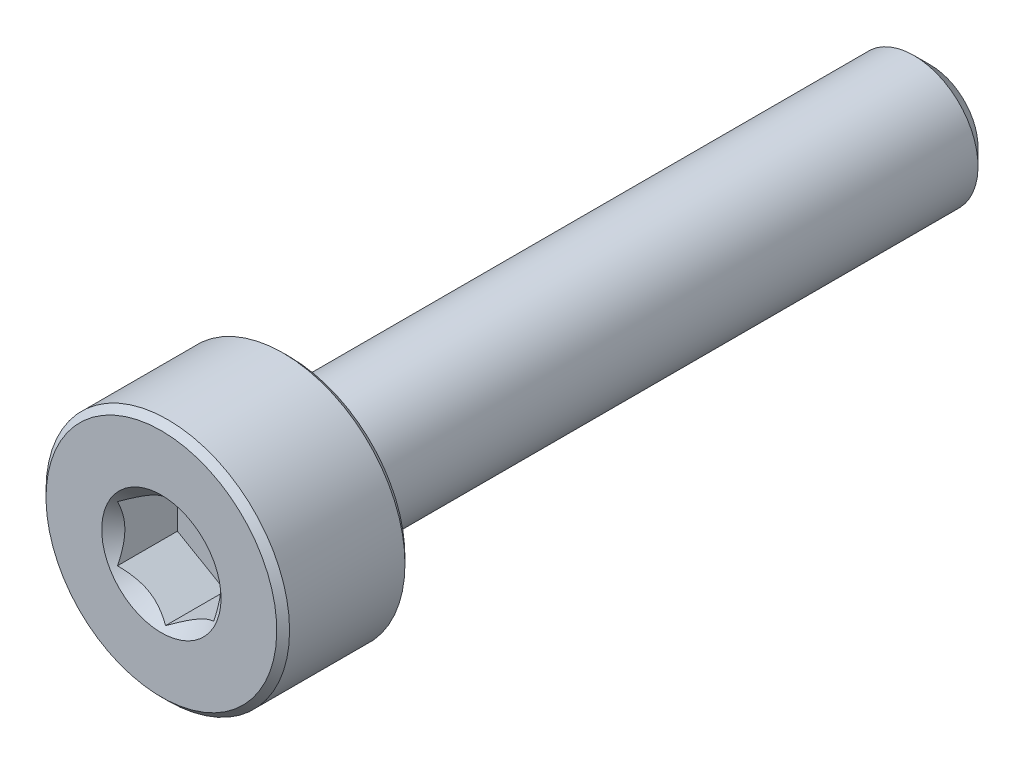
SolidWorks part; units mm, degrees
material "Alloy Steel (SS)"
ref_plane "Front Plane" through (0, 0, 0) normal (0, 0, 1) x (1, 0, 0)
ref_plane "Top Plane" through (0, 0, 0) normal (0, 1, 0) x (1, 0, 0)
ref_plane "Right Plane" through (0, 0, 0) normal (1, 0, 0) x (0, 0, -1)
sketch "Sketch1" plane through (0, 0, 0) normal (1, 0, 0) x (0, 0, -1)
  line L0 (-6, 0) -> (6, 0) construction
  line L1 (6, 0) -> (6, 0.7402) construction
  line L2 (6, 0.7402) -> (5.7402, 1) construction
  line L3 (5.7402, 1) -> (5.7, 1) construction
  line L4 (5.7, 1) -> (-4, 1) construction
  line L5 (-4, 1) -> (-4, 1.9) construction
  line L6 (-4, 1.9) -> (-6, 1.9) construction
  line L7 (-6, 1.9) -> (-6, 0) construction
  line L8 (6, 0.7402) -> (6, 1) construction
  line L9 (5.975, 1.0433) -> (6.175, 0.6969) construction
  line L10 (6.175, 0.6969) -> (6.375, 1.0433) construction
  line L11 (6.375, 1.0433) -> (5.975, 1.0433) construction
  line L12 (6.175, 1.0433) -> (6.175, 1) construction
  line L13 (6.175, 0.6969) -> (6.175, 0.7402) construction
  line L14 (6.15, 0.7402) -> (6.2, 0.7402) construction
  line L15 (6, 1) -> (6.35, 1) construction
  line L16 (5.9875, 1.0217) -> (6.3625, 1.0217) construction
  line L17 (6, 0) -> (6, -1) construction
  line L18 (-4.1, 1.9) -> (-4, 1.8) construction
  line L19 (-5.9, 1.9) -> (-6, 1.8) construction
  line L20 (-4, 1) -> (-4, 0) construction
  line L21 (-4, 0.5) -> (-0.6667, 0.5) construction
  line L22 (-0.6667, 0.5) -> (2.6667, 0.5) construction
  line L23 (2.6667, 0.5) -> (6, 0.5) construction
  line L24 (-0.6667, 0.5) -> (-0.6667, 1) construction
  line L25 (-0.6667, 1) -> (-0.6667, 1.9) construction
  line L26 (2.6667, 0.5) -> (2.6667, 1.9) construction
  point P0 (-6, 0.75)
  point P3 (5, 1)
  point P4 (0, 0)
  point P18 (2.6667, 1)
  point P22 (6.175, 0.7402)
  point P24 (5.7, 1)
  point P25 (6.175, 1)
  point P28 (6.175, 1.0217)
  point P29 (5, -1)
  point P30 (-0.6667, 1)
  point P31 (-5, 1.9)
  point P37 (-4.35, 1.9)
  point P38 (-5.85, 1.9)
  point P45 (-0.6667, 0.5)
  point P46 (2.6667, 0.5)
  dimension "D2" = 0.05
  dimension "D7" = 0.1
  dimension "D8" = 0.1
  dimension "D9" = 0.1
  dimension "D10" = 0.05
  dimension "D11" = 0.25
  dimension "Drive Size" = 1.5
  dimension "Head Diameter" = 3.8
  dimension "Head Height" = 2
  dimension "Thread Pitch" = 0.4
  dimension "Thread Dia" = 2
  dimension "Length" = 10
  dimension "D12" = 0.3
  dimension "D4" = 1
  dimension "D3" = 45
sketch "Sketch2" plane through (0, 0, 0) normal (1, 0, 0) x (0, 0, -1)
  line L0 (-6, 0) -> (-6, 1.8)
  line L1 (-5.9, 1.9) -> (-4.1, 1.9)
  line L2 (-4, 1.8) -> (-4, 1.1)
  line L4 (5.7402, 1) -> (6, 0.7402)
  line L5 (6, 0.7402) -> (6, 0)
  line L6 (-4, 1.9) -> (-6, 1.9) construction
  line L7 (6, 0) -> (-6, 0)
  line L8 (-5.9, 1.9) -> (-6, 1.8) construction
  line L10 (-5.9, 1.9) -> (-6, 1.8)
  line L14 (-4.1, 1.9) -> (-4, 1.8) construction
  line L16 (-4.1, 1.9) -> (-4, 1.8)
  line L17 (-4, 1) -> (-4, 1.9) construction
  line L19 (-3.9, 1) -> (5.7402, 1)
  line L20 (5.7, 1) -> (-4, 1) construction
  arc A1 (-4, 1.1) -> (-3.9, 1) centre (-3.9, 1.1) ccw
  dimension "D3" = 0.1
revolve "Revolve1" add sketch "Sketch2" angle 360 about L7
sketch "Sketch3" plane through (0, 0, 6) normal (0, 0, 1) x (1, 0, 0)
  line L1 (0.75, -0.433) -> (0.75, 0.433)
  line L2 (0.75, 0.433) -> (0, 0.866)
  line L3 (0, 0.866) -> (-0.75, 0.433)
  line L4 (-0.75, 0.433) -> (-0.75, -0.433)
  line L5 (-0.75, -0.433) -> (0, -0.866)
  line L6 (0, -0.866) -> (0.75, -0.433)
  circle A0 centre (0, 0) radius 0.75 construction
  circle A1 centre (0, 0) radius 1.9 construction
  circle A2 centre (0, 0) radius 1.9 construction
  circle A3 centre (0, 0) radius 0.866 construction
  point P13 (0, 0)
  dimension "D1" = 1.7321
extrude "Cut-Extrude1" cut sketch "Sketch3" against normal offset from surface (1 mm away) 1 up to face at (0, 1.8, 4)
sketch "Sketch4" plane through (0, 0, 6) normal (0, 0, 1) x (1, 0, 0)
  circle A0 centre (0, 0) radius 0.931
  dimension "D1" = 1.862
extrude "Cut-Extrude2" cut sketch "Sketch4" against normal up to vertex (1 mm away) draft 45 up to point (0, 1.9, 5)
sketch "Sketch11" plane through (0, 0, 0) normal (1, 0, 0) x (0, 0, -1)
  line L0 (-6, 0) -> (6, 0) construction
  line L1 (-6, 0) -> (6, 0) construction
  line L2 (-2.125, 0) -> (-2.125, 1) construction
  line L3 (5.7, 1) -> (-4, 1) construction
  line L4 (4.125, 0) -> (4.125, 1) construction
  line L6 (6, 0.7402) -> (6, 1) construction
  point P2 (-2.125, 0)
  point P3 (4.125, 0)
  dimension "D1" = 1.875
  dimension "D2" = 1.875
sketch "Sketch6" [suppressed] plane through (0, 0, -6) normal (0, 0, -1) x (-1, 0, 0)
  circle A0 centre (0, 0) radius 1
curve "Helix/Spiral1" [suppressed] pitch 0.4 height 10.4 turns 26
sketch "Sketch10" [suppressed] plane through (0, 0, 0) normal (1, 0, 0) x (0, 0, -1)
  line L0 (-3.9, -1.9) -> (-3.9, 1.9)
  line L5 (-6, 0) -> (6, 0) construction
  line L6 (-3.9, 1) -> (-3.9, -1) construction
  point P3 (-3.9, 0)
split "Split1" [suppressed] bodies to split 106
sketch "Sketch7" [suppressed] plane through (0, 0, 0) normal (1, 0, 0) x (0, 0, -1)
  line L0 (5.9875, 1.0217) -> (6.3625, 1.0217)
  line L1 (6.3625, 1.0217) -> (6.2, 0.7402)
  line L2 (6.2, 0.7402) -> (6.15, 0.7402)
  line L3 (6.15, 0.7402) -> (5.9875, 1.0217)
sweep "Cut-Sweep1" [suppressed] cut profiles "Sketch7" path "Helix/Spiral1"
sketch "Sketch8" [suppressed] plane through (0, 0, 0) normal (1, 0, 0) x (0, 0, -1)
  line L0 (-4, 0) -> (-4, 1)
  line L1 (-3.9, -1) -> (-3.9, 1) construction
  line L2 (-4, 1) -> (-3.9, 1)
  line L4 (-3.9, 1) -> (-3.3226, 0)
  line L5 (-3.3226, 0) -> (-4, 0)
  line L6 (5.7, 1) -> (-4, 1) construction
  line L7 (-6, 0) -> (6, 0) construction
  dimension "D1" = 60
revolve "Revolve2" [suppressed] add sketch "Sketch8" angle 360 about L5
equation "\"D2@Sketch1\" = \"Thread Pitch@Sketch1\" / 8"
equation "\"D4@Helix/Spiral1\" = \"Thread Pitch@Sketch1\""
equation "\"D7@Sketch1\" = \"Head Height@Sketch1\" * .05"
equation "\"D8@Sketch1\"=\"D7@Sketch1\""
equation "\"D9@Sketch1\"=\"D7@Sketch1\""
equation "\"D10@Sketch1\"=\"D7@Sketch1\"/2"
equation "\"D11@Sketch1\"=\"D10@Sketch1\"*5"
equation "\"D4@Sketch1\"=\"Thread Pitch@Sketch1\"*2.5"
equation "\"D12@Sketch1\"=\"Thread Pitch@Sketch1\"*.75"
equation "\"D3@Helix/Spiral1\"=\"Length@Sketch1\"+\"Thread Pitch@Sketch1\""
equation "\"D3@Sketch2\"=\"Thread Dia@Sketch1\"*0.05"
equation "\"D1@Sketch11\"=\"Length@Sketch1\"*0.1875"
equation "\"D2@Sketch11\"=\"D1@Sketch11\""
equation "\"D1@Sketch4\"=\"D1@Sketch3\"*1.075"
